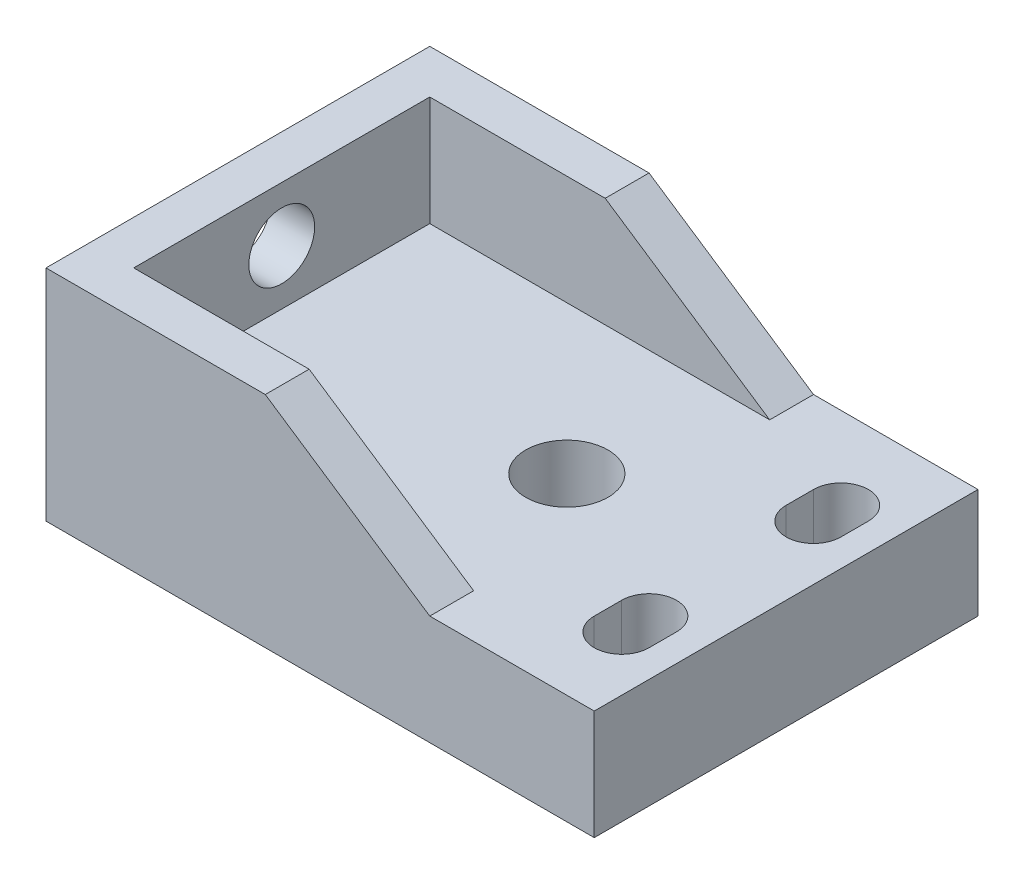
SolidWorks part; units mm, degrees
ref_plane "Спереди" through (0, 0, 0) normal (0, 0, 1) x (1, 0, 0)
ref_plane "Сверху" through (0, 0, 0) normal (0, 1, 0) x (1, 0, 0)
ref_plane "Справа" through (0, 0, 0) normal (1, 0, 0) x (0, 0, -1)
sketch "Эскиз1" plane through (0, 0, 0) normal (0, 0, 1) x (1, 0, 0)
  line L0 (50, 0) -> (20, 0)
  line L1 (-50, -20) -> (50, -20)
  line L2 (-50, -20) -> (-50, 20)
  line L3 (-50, 20) -> (50, 20)
  line L4 (50, -20) -> (50, 20)
  line L5 (-50, -20) -> (50, 20) construction
  line L6 (-50, 20) -> (50, -20) construction
  line L7 (20, 0) -> (-10, 20)
  point P0 (0, 0)
  dimension "D1" = 40
  dimension "D2" = 100
  dimension "D3" = 60
  dimension "D4" = 30
extrude "Бобышка-Вытянуть1" add sketch "Эскиз1" along normal blind 70 contours L0 L7 L3 L2 L1 L4 region at (-7.7419, -3.2258, 0)
sketch "Эскиз2" plane through (0, 20, 0) normal (0, 1, 0) x (1, 0, 0)
  line L0 (-50, -35) -> (50, -35) construction
  line L1 (-50, -70) -> (-50, 0) construction
  line L2 (50, -70) -> (50, 0) construction
  line L3 (-50, 0) -> (-10, 0) construction
  line L4 (42, -62) -> (-42, -62)
  line L5 (42, -62) -> (42, -8)
  line L6 (42, -8) -> (-42, -8)
  line L7 (-42, -62) -> (-42, -8)
  line L8 (42, -62) -> (-42, -8) construction
  line L9 (42, -8) -> (-42, -62) construction
  point P6 (0, -35)
  dimension "D1" = 8
  dimension "D2" = 8
extrude "Вырез-Вытянуть1" cut sketch "Эскиз2" against normal up to surface (20 mm away) up to face at (35, 0, 35)
sketch "Эскиз3" plane through (0, 0, 0) normal (0, 1, 0) x (1, 0, 0)
  line L0 (-50, -35) -> (50, -35) construction
  line L1 (-50, -70) -> (-50, 0) construction
  line L2 (50, -70) -> (50, 0) construction
  line L3 (50, -35) -> (50, 0) construction
  line L4 (50, -17.5) -> (-50, -17.5) construction
  line L5 (40, -20) -> (40, -15) construction
  line L6 (35, -20) -> (35, -15)
  line L7 (45, -20) -> (45, -15)
  circle A0 centre (10, -35) radius 7.5
  arc A1 (35, -20) -> (45, -20) centre (40, -20) ccw
  arc A2 (45, -15) -> (35, -15) centre (40, -15) ccw
  point P14 (40, -17.5)
  dimension "D1" = 15
  dimension "D2" = 40
  dimension "D3" = 10
  dimension "D4" = 10
  dimension "D5" = 5
extrude "Вырез-Вытянуть2" cut sketch "Эскиз3" against normal through all contours A0 region at (10, 0, 35)
extrude "Вырез-Вытянуть3" cut sketch "Эскиз3<4>" against normal through all contours A2 L6 A1 L7
sketch "Эскиз3<4>" plane through (0, 0, 0) normal (0, 1, 0) x (1, 0, 0) same geometry as "Эскиз3"
ref_plane "Плоскость1" through (0, 0, 35) normal (0, 0, -1) x (-1, 0, 0)
mirror "Зеркальное отражение1" about plane through (0, 0, 35) normal (0, 0, -1) of "Вырез-Вытянуть3"
sketch "Эскиз4" plane through (-42, 0, 0) normal (1, 0, 0) x (0, 0, -1)
  line L0 (-35, 20) -> (-35, 0) construction
  line L1 (-8, 20) -> (-62, 20) construction
  line L2 (-70, 0) -> (0, 0) construction
  circle A0 centre (-35, 10) radius 6
  dimension "D1" = 12
extrude "Вырез-Вытянуть4" cut sketch "Эскиз4" against normal through all
